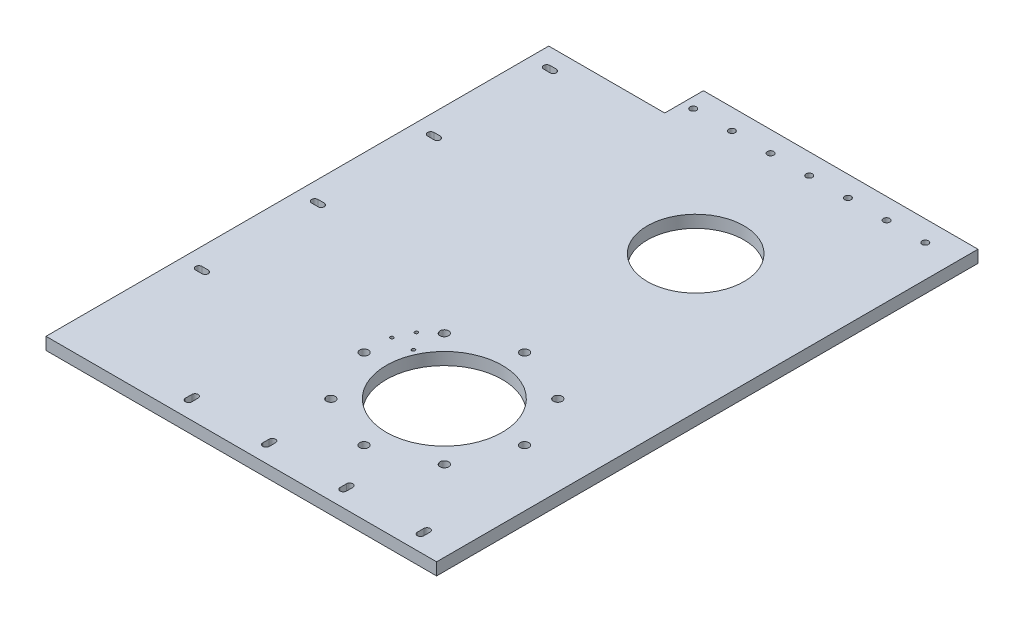
SolidWorks part; units mm, degrees
ref_plane "Front Plane" through (0, 0, 0) normal (0, 0, 1) x (1, 0, 0)
ref_plane "Top Plane" through (0, 0, 0) normal (0, 1, 0) x (1, 0, 0)
ref_plane "Right Plane" through (0, 0, 0) normal (1, 0, 0) x (0, 0, -1)
sketch "Sketch1" plane through (0, 0, 0) normal (0, 1, 0) x (1, 0, 0)
  line L3 (-71, 140) -> (71, 140)
  line L4 (71, -140) -> (71, 140)
  line L5 (0, 140) -> (0, -135) construction
  line L6 (0, 0) -> (71, 0) construction
  line L10 (-71, 140) -> (-71, 120)
  line L11 (-71, 120) -> (-131, 120)
  line L12 (-131, 120) -> (-131, -140)
  line L13 (-131, -140) -> (71, -140)
  point P0 (0, 0)
  dimension "D1" = 280
  dimension "D2" = 20
  dimension "D3" = 202
  dimension "D4" = 60
extrude "Boss-Extrude1" add sketch "Sketch1" along normal blind 6.35
sketch "Sketch2" plane through (0, 6.35, 0) normal (0, 1, 0) x (1, 0, 0)
  line L1 (0, 140) -> (0, -140) construction
  line L2 (71, 140) -> (-71, 140) construction
  line L3 (-131, -140) -> (71, -140) construction
  circle A0 centre (0, -65) radius 41.5 construction
  circle A1 centre (0, -23.5) radius 2.25
  circle A2 centre (29.3449, -35.6551) radius 2.25
  circle A3 centre (41.5, -65) radius 2.25
  circle A4 centre (29.3449, -94.3449) radius 2.25
  circle A5 centre (0, -106.5) radius 2.25
  circle A6 centre (-29.3449, -94.3449) radius 2.25
  circle A7 centre (-41.5, -65) radius 2.25
  circle A8 centre (-29.3449, -35.6551) radius 2.25
  circle A9 centre (0, -65) radius 80 construction
  circle A10 centre (0, -65) radius 30
  point P22 (0, -65)
  dimension "D1" = 83
  dimension "D2" = 4.5
  dimension "D4" = 160
  dimension "D6" = 60
  dimension "D5" = 75
  dimension "D3" = 8
extrude "Cut-Extrude1" cut sketch "Sketch2" against normal through all
sketch "Sketch6" plane through (0, 6.35, 0) normal (0, 1, 0) x (1, 0, 0)
  line L0 (0, -65) -> (-38.9712, -46.8274) construction
  line L1 (0, -65) -> (0, -23.5) construction
  line L2 (-40.9787, -51.1324) -> (-36.9638, -42.5225) construction
  line L3 (-36.9638, -42.5225) -> (-27.9007, -46.7486) construction
  circle A0 centre (0, -65) radius 30 construction
  circle A1 centre (-36.9638, -42.5225) radius 0.85
  circle A2 centre (-40.9787, -51.1324) radius 0.85
  circle A5 centre (-29.9082, -51.0536) radius 0.85
  point P7 (-38.9712, -46.8274)
  dimension "D4" = 1.7
  dimension "D5" = 10
  dimension "D7" = 10
  dimension "D6" = 1.7
  dimension "D1" = 43
  dimension "D2" = 9.5
  dimension "D3" = 65
extrude "Cut-Extrude5" cut sketch "Sketch6" against normal through all
sketch "Sketch8" plane through (0, 6.35, 0) normal (0, 1, 0) x (1, 0, 0)
  line L1 (71, 140) -> (-71, 140) construction
  line L2 (65, -20.6305) -> (65, 140) construction
  line L3 (71, -140) -> (71, 140) construction
  line L5 (45, 41.8036) -> (45, 140) construction
  circle A0 centre (0, 65) radius 25
  circle A1 centre (0, -65) radius 30 construction
  dimension "D1" = 130
  dimension "D2" = 50
  dimension "D3" = 6
  dimension "D4" = 20
extrude "Cut-Extrude9" cut sketch "Sketch8" against normal through all
sketch "Sketch9" plane through (0, 0, 0) normal (0, -1, 0) x (-1, 0, 0)
  circle A1 centre (45.6, 129.325) radius 1.65
  circle A2 centre (5.6, 129.325) radius 1.65
  circle A3 centre (-34.4, 129.325) radius 1.65
  circle A4 centre (65.6, 129.325) radius 1.65
  circle A5 centre (25.6, 129.325) radius 1.65
  circle A6 centre (-14.4, 129.325) radius 1.65
  circle A7 centre (-54.4, 129.325) radius 1.65
extrude "Cut-Extrude10" cut sketch "Sketch9" against normal blind 30
sketch "Sketch10" plane through (0, 0, 0) normal (0, -1, 0) x (1, 0, 0)
  line L0 (-121.975, 10) -> (-118.675, 10) construction
  line L3 (-121.975, 11.65) -> (-118.675, 11.65)
  line L4 (-121.975, 8.35) -> (-118.675, 8.35)
  line L5 (-121.975, 70) -> (-118.675, 70) construction
  line L6 (-121.975, 71.65) -> (-118.675, 71.65)
  line L7 (-121.975, 68.35) -> (-118.675, 68.35)
  line L8 (-121.975, -50) -> (-118.675, -50) construction
  line L9 (-121.975, -48.35) -> (-118.675, -48.35)
  line L10 (-121.975, -51.65) -> (-118.675, -51.65)
  line L11 (-121.975, -110) -> (-118.675, -110) construction
  line L12 (-121.975, -108.35) -> (-118.675, -108.35)
  line L13 (-121.975, -111.65) -> (-118.675, -111.65)
  circle A0 centre (-120.325, -110) radius 1.65
  circle A1 centre (-120.325, -50) radius 1.65
  circle A2 centre (-120.325, 10) radius 1.65
  circle A3 centre (-120.325, 70) radius 1.65
  arc A6 (-121.975, 11.65) -> (-121.975, 8.35) centre (-121.975, 10) ccw
  arc A7 (-118.675, 8.35) -> (-118.675, 11.65) centre (-118.675, 10) ccw
  arc A8 (-121.975, 71.65) -> (-121.975, 68.35) centre (-121.975, 70) ccw
  arc A9 (-118.675, 68.35) -> (-118.675, 71.65) centre (-118.675, 70) ccw
  arc A10 (-121.975, -48.35) -> (-121.975, -51.65) centre (-121.975, -50) ccw
  arc A11 (-118.675, -51.65) -> (-118.675, -48.35) centre (-118.675, -50) ccw
  arc A12 (-121.975, -108.35) -> (-121.975, -111.65) centre (-121.975, -110) ccw
  arc A13 (-118.675, -111.65) -> (-118.675, -108.35) centre (-118.675, -110) ccw
  point P14 (-120.325, 10)
  point P21 (-120.325, 70)
  point P28 (-120.325, -50)
  point P35 (-120.325, -110)
  dimension "D1" = 3.3
  dimension "D2" = 3.3
  dimension "D3" = 3.3
  dimension "D4" = 3.3
  dimension "D5" = 1.65
  dimension "D6" = 1.65
  dimension "D7" = 1.65
  dimension "D8" = 1.65
sketch "Sketch11" plane through (0, 6.35, 0) normal (0, 1, 0) x (1, 0, 0)
  line L0 (71, -127.15) -> (-131, -127.15) construction
  line L1 (71, -140) -> (71, 140) construction
  line L2 (456.625, -127.15) -> (-127.825, -127.15) construction
  line L3 (-131, 120) -> (-131, -140) construction
  line L4 (71, -132.85) -> (-131, -132.85) construction
  line L5 (456.625, -132.85) -> (-127.825, -132.85) construction
  line L6 (-65.6, 129.325) -> (-65.6, -130.005) construction
  line L7 (-65.6, -130.005) -> (71, -130) construction
  line L8 (456.625, -130) -> (-127.825, -130) construction
  line L9 (-25.6, 129.325) -> (-25.6, -130.0035) construction
  line L10 (14.4, 129.325) -> (14.4, -130.0021) construction
  line L11 (54.4, 129.325) -> (54.4, -130.0006) construction
  line L12 (-65.6, -128.355) -> (-65.6, -131.655) construction
  line L13 (-63.95, -128.355) -> (-63.95, -131.655)
  line L14 (-67.25, -128.355) -> (-67.25, -131.655)
  line L15 (-25.6, -128.3535) -> (-25.6, -131.6535) construction
  line L16 (-23.95, -128.3535) -> (-23.95, -131.6535)
  line L17 (-27.25, -128.3535) -> (-27.25, -131.6535)
  line L18 (14.4, -128.3521) -> (14.4, -131.6521) construction
  line L19 (16.05, -128.3521) -> (16.05, -131.6521)
  line L20 (12.75, -128.3521) -> (12.75, -131.6521)
  line L21 (54.4, -128.3506) -> (54.4, -131.6506) construction
  line L22 (56.05, -128.3506) -> (56.05, -131.6506)
  line L23 (52.75, -128.3506) -> (52.75, -131.6506)
  circle A0 centre (-65.6, -130.005) radius 1.65 construction
  circle A1 centre (-25.6, -130.0035) radius 1.65 construction
  circle A2 centre (14.4, -130.0021) radius 1.65 construction
  circle A3 centre (54.4, -130.0006) radius 1.65 construction
  arc A4 (-63.95, -128.355) -> (-67.25, -128.355) centre (-65.6, -128.355) ccw
  arc A5 (-67.25, -131.655) -> (-63.95, -131.655) centre (-65.6, -131.655) ccw
  arc A6 (-23.95, -128.3535) -> (-27.25, -128.3535) centre (-25.6, -128.3535) ccw
  arc A7 (-27.25, -131.6535) -> (-23.95, -131.6535) centre (-25.6, -131.6535) ccw
  arc A8 (16.05, -128.3521) -> (12.75, -128.3521) centre (14.4, -128.3521) ccw
  arc A9 (12.75, -131.6521) -> (16.05, -131.6521) centre (14.4, -131.6521) ccw
  arc A10 (56.05, -128.3506) -> (52.75, -128.3506) centre (54.4, -128.3506) ccw
  arc A11 (52.75, -131.6506) -> (56.05, -131.6506) centre (54.4, -131.6506) ccw
  point P33 (-65.6, -130.005)
  point P39 (-25.6, -130.0035)
  point P46 (14.4, -130.0021)
  point P53 (54.4, -130.0006)
  dimension "D2" = 3.3
  dimension "D1" = 259.33
extrude "Cut-Extrude12" cut sketch "Sketch11" against normal blind 30
extrude "Cut-Extrude13" cut sketch "Sketch10" against normal blind 10 contours A0 | L13 A13 L12 A0 | L12 A12 L13 A0 | L9 A10 L10 A1 | A1 | L10 A11 L9 A1 | L3 A6 L4 A2 | A2 | L4 A7 L3 A2 | L6 A8 L7 A3 | A3 | L7 A9 L6 A3 region at (-122.4459, 0, 10) region at (-118.2041, 0, 10) region at (-120.325, 0, 10) region at (-122.4459, 0, 70) region at (-118.2041, 0, 70) region at (-120.325, 0, 70) region at (-122.4459, 0, -50) region at (-118.2041, 0, -50) region at (-120.325, 0, -50) region at (-122.4459, 0, -110) region at (-118.2041, 0, -110) region at (-120.325, 0, -110)
